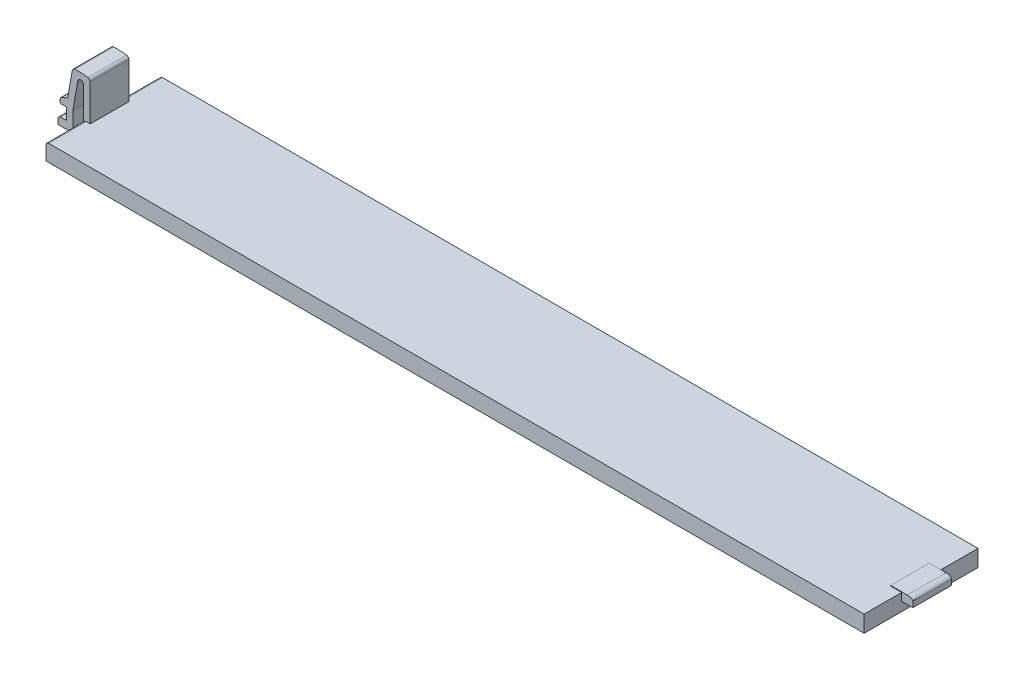
SolidWorks part; units mm, degrees
ref_plane "前视基准面" through (0, 0, 0) normal (0, 0, 1) x (1, 0, 0)
ref_plane "上视基准面" through (0, 0, 0) normal (0, 1, 0) x (1, 0, 0)
ref_plane "右视基准面" through (0, 0, 0) normal (1, 0, 0) x (0, 0, -1)
other "Configuration Table"
sketch "草图1" plane through (0, 0, 0) normal (0, 1, 0) x (1, 0, 0)
  line L1 (-74, 10.3) -> (74, 10.3)
  line L2 (-74, 10.3) -> (-74, -10.3)
  line L3 (-74, -10.3) -> (74, -10.3)
  line L4 (74, 10.3) -> (74, -10.3)
  line L5 (-74, 10.3) -> (74, -10.3) construction
  line L6 (-74, -10.3) -> (74, 10.3) construction
  point P0 (0, 0)
  dimension "D1" = 148
  dimension "D2" = 20.6
extrude "凸台-拉伸1" add sketch "草图1" along normal blind 3
sketch "草图2" plane through (0, 3, 0) normal (0, 1, 0) x (1, 0, 0)
  line L0 (74, -10.3) -> (74, 10.3) construction
  line L1 (72, 3.5) -> (76, 3.5)
  line L2 (72, 3.5) -> (72, -3.5)
  line L3 (72, -3.5) -> (76, -3.5)
  line L4 (76, 3.5) -> (76, -3.5)
  line L5 (74, 0) -> (63.5421, 0) construction
  dimension "D1" = 2
  dimension "D2" = 2
  dimension "D3" = 7
extrude "凸台-拉伸2" add sketch "草图2" along normal blind 1.5 from offset 1.4 offset against normal yes
sketch "草图5" plane through (0, 0, 10.3) normal (0, 0, 1) x (1, 0, 0)
  line L0 (-74, 3) -> (-74, 9)
  line L1 (-74.9616, 9.0287) -> (-75.9365, 3.5)
  line L3 (-76.894, 4.9803) -> (-75.989, 10.1127)
  line L4 (-72.8, 3) -> (-72.8, 10)
  line L5 (-74, 3) -> (74, 3) construction
  line L6 (-74, 0) -> (-75.5, 0) construction
  line L7 (-74, 3) -> (-74, 0) construction
  line L8 (-72.8, 3) -> (-74, 3)
  line L9 (-77.1365, 3.5) -> (-75.9365, 3.5) construction
  line L11 (-75.9365, 3.5) -> (-75.9365, 0)
  line L12 (91.1, 3) -> (77.1, 3) construction
  line L13 (-77.1365, 3.5) -> (-77.1365, 1.4)
  line L14 (-77.2, 0) -> (-75.9365, 0)
  line L15 (-77.1365, 3.5) -> (-78.2365, 3.5)
  line L16 (-78.2365, 3.5) -> (-78.2365, 4.5)
  line L17 (-78.2365, 4.5) -> (-76.894, 4.9803)
  line L19 (-78.6365, 1.4) -> (-77.1365, 1.4)
  line L20 (-78.6365, 1.4) -> (-78.6365, 0)
  line L21 (-78.6365, 0) -> (-77.2, 0)
  arc A0 (-74.9616, 9.0287) -> (-74, 9) centre (-74.75, 0) cw
  arc A1 (-72.8, 10) -> (-75.989, 10.1127) centre (-74.75, 0) ccw
  dimension "D1" = 1.2
  dimension "D2" = 1.2
  dimension "D3" = 10
  dimension "D4" = 7
  dimension "D5" = 6
  dimension "D6" = 1.5
  dimension "D7" = 2
  dimension "D8" = 1.5
  dimension "D9" = 1
  dimension "D10" = 1.1
  dimension "D11" = 1.2
  dimension "D12" = 1.4
  dimension "D13" = 1.5
  dimension "D14" = 0.5
extrude "凸台-拉伸4" add sketch "草图5" along normal mid plane 7 from surface starting at plane "前视基准面"
fillet "圆角2" radius 0.5 1 edges at (76, 3.1, 0) second distance 1 first distance on face at (76, 2.35, 0)
sketch "草图6" plane through (-78.2365, 0, 0) normal (-1, 0, 0) x (0, 0, 1)
  line L1 (-1.5, 4.9803) -> (1.5, 4.9803)
  line L2 (-1.5, 4.9803) -> (-1.5, 3.5)
  line L3 (-1.5, 3.5) -> (1.5, 3.5)
  line L4 (1.5, 4.9803) -> (1.5, 3.5)
  line L5 (3.5, 3.5) -> (-3.5, 3.5) construction
  line L6 (3.5, 4.5) -> (3.5, 3.5) construction
  line L7 (-3.5, 4.5) -> (-3.5, 3.5) construction
  line L8 (3.5, 4.9803) -> (-3.5, 4.9803) construction
  dimension "D1" = 2
  dimension "D2" = 2
extrude "切除-拉伸1" cut sketch "草图6" against normal up to surface (1.3425 mm away) up to face at (-76.4415, 7.5465, 0)
fillet "圆角3" radius 0.5 9 edges at (-74, 9, 0) (-74.9616, 9.0287, 0) (-72.8, 10, 0) (-75.989, 10.1127, 0) (-78.6365, 1.4, 0) (-78.2365, 4.5, -2.5) (-78.2365, 4.5, 2.5) (-74, 3, -6.9) (-74, 3, 6.9)
fillet "圆角4" radius 0.2 2 edges at (-78.2365, 3.5, 2.5) (-78.2365, 3.5, -2.5)
